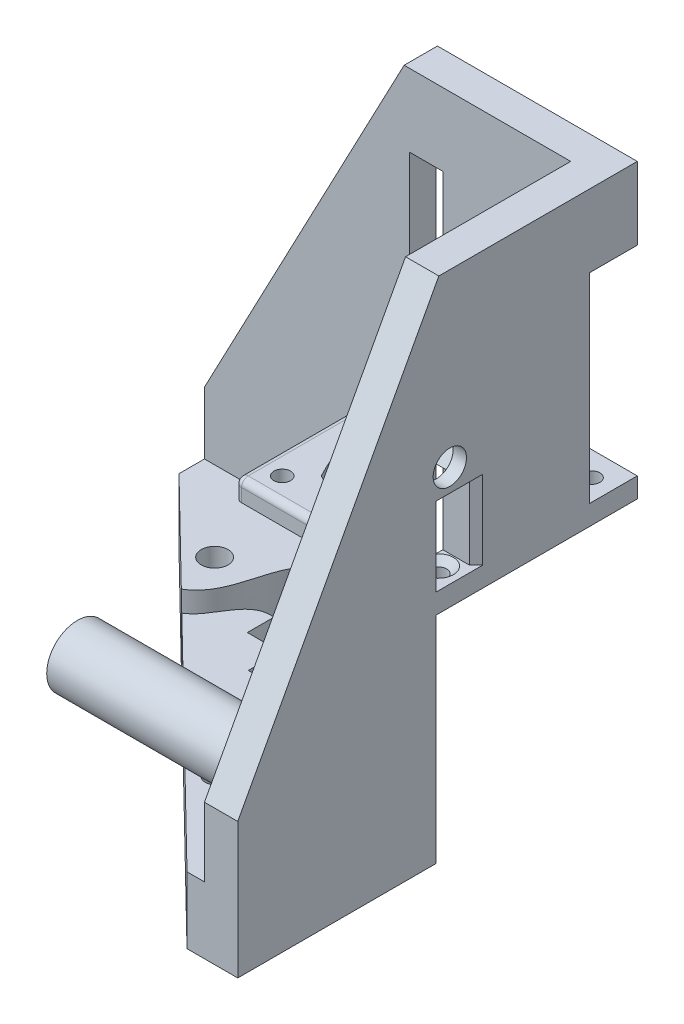
SolidWorks part; units mm, degrees
ref_plane "Front" through (0, 0, 0) normal (0, 0, 1) x (1, 0, 0)
ref_plane "Top" through (0, 0, 0) normal (0, 1, 0) x (1, 0, 0)
ref_plane "Right" through (0, 0, 0) normal (1, 0, 0) x (0, 0, -1)
sketch "Sketch1" plane through (0, 0, 0) normal (0, 1, 0) x (1, 0, 0)
  line L0 (-34.4663, 5.5479) -> (17.9137, -45.6289)
  line L1 (-34.4663, 14.3711) -> (25.5337, 14.3711)
  line L2 (-34.4663, 14.3711) -> (-34.4663, -45.6289)
  line L3 (-34.4663, -45.6289) -> (25.5337, -45.6289)
  line L4 (25.5337, 14.3711) -> (25.5337, -45.6289)
  circle A0 centre (7.6521, -31.0695) radius 1.5601
  circle A1 centre (-20.9229, -2.6469) radius 2.0092
  dimension "D3" = 17.8816
  dimension "D4" = 45.4406
  dimension "D5" = 17.018
  dimension "D6" = 46.4566
  dimension "D1" = 60
  dimension "D2" = 60
extrude "Boss-Extrude1" add sketch "Sketch1" along normal blind 10 contours L4 L1 L2 L0 L3
sketch "Sketch3" plane through (0, 10, 0) normal (0, 1, 0) x (1, 0, 0)
  line L0 (-34.4663, 9.3711) -> (20.5337, 9.3711)
  line L1 (20.5337, 9.3711) -> (20.5337, -45.6289)
  line L5 (25.5337, -45.6289) -> (25.5337, 14.3711)
  line L6 (25.5337, 14.3711) -> (-34.4663, 14.3711)
  line L7 (-34.4663, 14.3711) -> (-34.4663, 5.5479)
  line L8 (-34.4663, 5.5479) -> (17.9137, -45.6289)
  line L9 (17.9137, -45.6289) -> (25.5337, -45.6289)
  line L10 (25.5337, -45.6289) -> (25.5337, 14.3711)
  line L11 (25.5337, 14.3711) -> (-34.4663, 14.3711)
  line L12 (-34.4663, 14.3711) -> (-34.4663, 5.5479)
  line L13 (-34.4663, 5.5479) -> (17.9137, -45.6289)
  line L14 (17.9137, -45.6289) -> (25.5337, -45.6289)
  line M8 (25.5337, -45.6289) -> (25.5337, 14.3711)
  line M9 (25.5337, 14.3711) -> (-34.4663, 14.3711)
  line M10 (-34.4663, 14.3711) -> (-34.4663, 5.5479)
  line M12 (17.9137, -45.6289) -> (25.5337, -45.6289)
  dimension "D2" = 5
  dimension "D3" = 5
  dimension "D1" = 0
extrude "Boss-Extrude3" add sketch "Sketch3" along normal blind 76.2 from surface at -10 contours L0 L1 M12 M8 M9 M10 | L11 L12 L13 L14 L10
sketch "Sketch4" plane through (0, 10, 0) normal (0, 1, 0) x (1, 0, 0)
  line L1 (25.5337, 14.3711) -> (-3.6763, 14.3711)
  line L2 (25.5337, 14.3711) -> (25.5337, -14.8389)
  line L3 (25.5337, -14.8389) -> (-3.6763, -14.8389)
  line L4 (-3.6763, 14.3711) -> (-3.6763, -14.8389)
  line L5 (20.5337, -45.6289) -> (20.5337, 9.3711)
  line L6 (-34.4663, 9.3711) -> (20.5337, 9.3711)
  line L7 (20.5337, 9.3711) -> (20.5337, -45.6289)
  line L8 (20.5337, -45.6289) -> (25.5337, -45.6289)
  line L9 (25.5337, -45.6289) -> (25.5337, 14.3711)
  line L10 (25.5337, 14.3711) -> (-34.4663, 14.3711)
  line L11 (-34.4663, 14.3711) -> (-34.4663, 9.3711)
  line L12 (-34.4663, 9.3711) -> (20.5337, 9.3711)
  line L13 (20.5337, 9.3711) -> (20.5337, -45.6289)
  line L14 (20.5337, -45.6289) -> (25.5337, -45.6289)
  line L15 (25.5337, -45.6289) -> (25.5337, 14.3711)
  line L16 (25.5337, 14.3711) -> (-34.4663, 14.3711)
  line L17 (-34.4663, 14.3711) -> (-34.4663, 9.3711)
  line L18 (20.5337, 9.3711) -> (-34.4663, 9.3711)
  line L19 (-34.4663, 9.3711) -> (-34.4663, 5.5479)
  line L20 (-34.4663, 5.5479) -> (17.9137, -45.6289)
  line L21 (17.9137, -45.6289) -> (20.5337, -45.6289)
  line L22 (20.5337, -45.6289) -> (20.5337, 9.3711)
  line L23 (20.5337, 9.3711) -> (-34.4663, 9.3711)
  line L24 (-34.4663, 9.3711) -> (-34.4663, 5.5479)
  line L25 (-34.4663, 5.5479) -> (17.9137, -45.6289)
  line L26 (17.9137, -45.6289) -> (20.5337, -45.6289)
  dimension "D3" = 29.21
  dimension "D4" = 29.21
  dimension "D1" = 0
  dimension "D2" = 0
extrude "Cut-Extrude1" cut sketch "Sketch4" against normal up to next and the other way blind 22.3 contours L1 L4 L3 L2
sketch "Sketch5" plane through (0, 32.3, 0) normal (0, -1, 0) x (1, 0, 0)
  line L0 (-3.6763, 14.8389) -> (25.5337, 14.8389) construction
  line L1 (-3.6763, 14.8389) -> (-3.6763, -14.3711) construction
  line L2 (25.5337, -14.3711) -> (-3.6763, -14.3711) construction
  line L3 (25.5337, -14.3711) -> (25.5337, 14.8389) construction
  line L4 (-3.6763, 14.8389) -> (25.5337, 14.8389)
  line L5 (-3.6763, 14.8389) -> (-3.6763, -14.3711)
  line L6 (25.5337, -14.3711) -> (-3.6763, -14.3711)
  line L7 (25.5337, -14.3711) -> (25.5337, 14.8389)
  line L9 (21.8237, 12.3389) -> (-1.1763, 12.3389)
  line L10 (21.8237, 12.3389) -> (21.8237, -10.6611)
  line L11 (21.8237, -10.6611) -> (-1.1763, -10.6611)
  line L12 (-1.1763, 12.3389) -> (-1.1763, -10.6611)
  line L13 (25.5337, -14.3711) -> (19.3237, -14.3711)
  line L14 (25.5337, -14.3711) -> (25.5337, -8.1611)
  line L15 (25.5337, -8.1611) -> (19.3237, -8.1611)
  line L16 (19.3237, -14.3711) -> (19.3237, -8.1611)
  line L17 (-3.6763, -14.3711) -> (1.3237, -14.3711)
  line L18 (-3.6763, -14.3711) -> (-3.6763, -8.1611)
  line L19 (-3.6763, -8.1611) -> (1.3237, -8.1611)
  line L20 (1.3237, -14.3711) -> (1.3237, -8.1611)
  line L21 (25.5337, 14.8389) -> (19.3237, 14.8389)
  line L22 (25.5337, 14.8389) -> (25.5337, 9.8389)
  line L23 (25.5337, 9.8389) -> (19.3237, 9.8389)
  line L24 (19.3237, 14.8389) -> (19.3237, 9.8389)
  line M10 (20.5337, -9.3711) -> (-3.6763, -9.3711)
  line M11 (-3.6763, -9.3711) -> (-3.6763, -14.3711)
  line M12 (-3.6763, -14.3711) -> (25.5337, -14.3711)
  line M13 (25.5337, -14.3711) -> (25.5337, 14.8389)
  line M15 (20.5337, 14.8389) -> (20.5337, -9.3711)
  dimension "D1" = 23
  dimension "D2" = 23
  dimension "D3" = 2.5
  dimension "D4" = 2.5
  dimension "D5" = 2.5
  dimension "D6" = 2.5
  dimension "D7" = 2.5
  dimension "D8" = 2.5
  dimension "D9" = 2.5
extrude "Cut-Extrude2" cut sketch "Sketch5" against normal blind 30 from offset 3 contours L20 L11 L12 M12 M10 M11 | L11 L20 L12 M10 | L20 L19 L12 M10 | L16 L6 L15 L10 L11 M13 | L16 L11 L10 L15 M15 M10 | L16 L15 M10 M15 offset against normal yes
sketch "Sketch6" plane through (0, 32.3, 0) normal (0, -1, 0) x (1, 0, 0)
  line L1 (-3.6763, 14.8389) -> (25.5337, 14.8389) construction
  line L2 (-3.6763, 14.8389) -> (-3.6763, -14.3711) construction
  circle A0 centre (22.3237, 12.2889) radius 1.25
  circle A2 centre (22.3237, -10.7111) radius 1.25
  circle A3 centre (-0.6763, -10.7111) radius 1.25
  dimension "D1" = 2.55
  dimension "D2" = 26
  dimension "D3" = 2.5
  dimension "D4" = 23
  dimension "D5" = 23
extrude "Cut-Extrude3" cut sketch "Sketch6" against normal up to next
chamfer "Chamfer1" distance 1 angle 45 8 edges at (-3.6763, 16.15, -14.3711) (1.3237, 50.3, -14.3711) (19.3237, 50.3, -14.3711) (25.5337, 50.3, -8.1611) (25.5337, 50.3, 9.8389) (25.5337, 16.15, 14.8389) (-3.6763, 50.3, -14.3711) (25.5337, 50.3, 14.8389)
sketch "Sketch7" plane through (0, 0, -9.3711) normal (0, 0, 1) x (1, 0, 0)
  line L0 (-4.4781, 76.2) -> (-34.4663, 19.3455)
  line L1 (-34.4663, 76.2) -> (20.5337, 76.2) construction
  line L2 (-34.4663, 76.2) -> (-34.4663, 10) construction
  line L3 (-34.4663, 19.3455) -> (-34.4663, 76.2)
  line L4 (-34.4663, 76.2) -> (-4.4781, 76.2)
extrude "Cut-Extrude4" cut sketch "Sketch7" against normal up to next
sketch "Sketch8" plane through (20.5337, 0, 0) normal (-1, 0, 0) x (0, 0, 1)
  line L0 (15.4321, 76.2) -> (45.6289, 20.3609)
  line L1 (-9.3711, 76.2) -> (45.6289, 76.2) construction
  line L2 (45.6289, 76.2) -> (45.6289, 10) construction
  line L3 (45.6289, 20.3609) -> (45.6289, 76.2)
  line L4 (45.6289, 76.2) -> (15.4321, 76.2)
  line L5 (-5.5479, 10) -> (45.6289, 10) construction
  circle A0 centre (34.7196, 18.9535) radius 2.6
  line M15 (45.6289, 10) -> (45.6289, 76.2)
  line M16 (45.6289, 76.2) -> (-9.3711, 76.2)
  dimension "D1" = 10.9093
  dimension "D3" = 5.2
  dimension "D2" = 8.9535
extrude "Cut-Extrude5" cut sketch "Sketch8" against normal up to next contours L0 M16 M15
sketch "Sketch9" plane through (0, 32.3, 0) normal (0, -1, 0) x (1, 0, 0)
  line L0 (-4.6763, -14.3711) -> (-4.6763, 15.8389)
  line L1 (-4.6763, 15.8389) -> (25.5337, 15.8389)
  line L2 (25.5337, -14.3711) -> (-13.9259, 25.0885) construction
  line L3 (25.5337, -14.3711) -> (-4.6763, -14.3711) construction
  line L4 (-4.6763, -14.3711) -> (0.9008, -14.3711)
  line L5 (25.5337, 10.2619) -> (25.5337, 15.8389)
  line L6 (25.5337, -14.3711) -> (25.5337, 15.8389) construction
  arc A0 (0.9008, -14.3711) -> (1.8042, 9.3584) centre (25.0313, -3.4078) cw
  arc A1 (25.5337, 10.2619) -> (1.8042, 9.3584) centre (14.5705, -13.8686) ccw
  circle A2 centre (-0.6763, -10.7111) radius 1.25 construction
  circle A3 centre (22.3237, 12.2889) radius 1.25 construction
  circle A4 centre (-0.6763, -10.7111) radius 1.25
  circle A5 centre (22.3237, 12.2889) radius 1.25
  circle A6 centre (-1.1263, 12.2889) radius 1.25
  circle M8 centre (22.3237, 12.2889) radius 1.25
  circle M9 centre (-0.6763, -10.7111) radius 1.25
  line M11 (20.5337, -9.3711) -> (-3.6763, -9.3711)
  line M12 (-3.6763, -9.3711) -> (-3.6763, -13.3711)
  line M13 (-3.6763, -13.3711) -> (-4.6763, -14.3711)
  line M14 (-4.6763, -14.3711) -> (25.5337, -14.3711)
  line M15 (25.5337, -14.3711) -> (25.5337, 15.8389)
  line M16 (25.5337, 15.8389) -> (24.5337, 14.8389)
  line M17 (24.5337, 14.8389) -> (20.5337, 14.8389)
  line M18 (20.5337, 14.8389) -> (20.5337, -9.3711)
  dimension "D1" = 5.5771
extrude "Boss-Extrude4" add sketch "Sketch9" against normal blind 3 contours A0 M14 M9 M11 M12 M13 | A1 M15 M16 M17 M18 M8 | L2 A1 L1 M18 M17 M16 | A0 L2 L0 M13 M12 M11
fillet "Fillet2" radius 1 4 edges at (7.9287, 35.3, 15.8389) (-4.6763, 35.3, 3.2339) (-4.6763, 33.8, 15.8389) (-0.7934, 33.8, -9.3711)
sketch "Sketch10" plane through (0, 32.3, 0) normal (0, -1, 0) x (1, 0, 0)
  line L0 (22.3237, 12.2889) -> (-0.6763, -10.7111) construction
  circle A0 centre (10.8237, 0.7889) radius 11.5
extrude "Cut-Extrude6" cut sketch "Sketch10" against normal blind 3
sketch "Sketch12" plane through (20.5337, 0, 0) normal (-1, 0, 0) x (0, 0, 1)
  line L0 (45.6289, 20.3609) -> (45.6289, 10) construction
  line L1 (-5.5479, 10) -> (45.6289, 10) construction
  circle A0 centre (34.7189, 18.95) radius 2.6
  circle A1 centre (34.7189, 18.95) radius 4.6
  dimension "D1" = 10.91
  dimension "D2" = 8.95
  dimension "D3" = 5.2
  dimension "D4" = 2
extrude "Boss-Extrude5" add sketch "Sketch12" along normal blind 30
fillet "Fillet3" radius 1 1 edges at (-9.4663, 18.95, 37.3189)
chamfer "Chamfer2" distance 1 angle 45 2 edges at (22.3237, 35.3, 13.5389) (-0.6763, 35.3, -11.9611)
sketch "Sketch14" plane through (25.5337, 0, 0) normal (1, 0, 0) x (0, 0, -1)
  line L1 (-19.4539, 65.849) -> (-7.0581, 65.849)
  line L2 (-19.4539, 65.849) -> (-19.4539, 47.1223)
  line L3 (-19.4539, 47.1223) -> (-7.0581, 47.1223)
  line L4 (-7.0581, 65.849) -> (-7.0581, 47.1223)
extrude "Boss-Extrude6" add sketch "Sketch14" against normal up to surface (5 mm away) up to face at (20.5337, 18.95, 30.1189)
sketch "Sketch13" plane through (25.5337, 0, 0) normal (1, 0, 0) x (0, 0, -1)
  line L0 (33, 0) -> (-33, 0) construction
  line L2 (14.3711, 76.2) -> (14.3711, 65.3) construction
  circle A0 centre (-13.7829, 50.506) radius 2.5
  dimension "D1" = 50.506
  dimension "D2" = 5
  dimension "D3" = 28.154
extrude "Cut-Extrude7" cut sketch "Sketch13" against normal blind 20
sketch "Sketch15" plane through (20.5337, 0, 0) normal (-1, 0, 0) x (0, 0, 1)
  line L1 (16.1501, 46.406) -> (18.5172, 50.506)
  line L2 (18.5172, 50.506) -> (16.1501, 54.606)
  line L3 (16.1501, 54.606) -> (11.4158, 54.606)
  line L4 (11.4158, 54.606) -> (9.0487, 50.506)
  line L5 (9.0487, 50.506) -> (11.4158, 46.406)
  line L6 (11.4158, 46.406) -> (16.1501, 46.406)
  circle A0 centre (13.7829, 50.506) radius 4.1 construction
  dimension "D1" = 8.2
extrude "Cut-Extrude8" cut sketch "Sketch15" against normal blind 3
sketch "Sketch19" plane through (0, 10, 0) normal (0, 1, 0) x (1, 0, 0)
  line L0 (-3.6763, -14.8389) -> (-3.6763, 9.3711) construction
  line L3 (-3.6763, 2.8577) -> (-3.5286, -1.6399)
  line L4 (-34.4663, 5.5479) -> (17.9137, -45.6289) construction
  line L5 (-3.6763, 7.518) -> (-8.6763, 7.518)
  line L6 (-3.6763, 7.518) -> (-3.6763, -9.982)
  line L7 (-3.6763, -9.982) -> (-8.6763, -9.982)
  line L8 (-8.6763, 7.518) -> (-8.6763, -9.982)
  line L9 (-19.2829, -9.2868) -> (-16.1211, -12.3759)
  spline S0 degree 3 poles (-8.6763, 5.1248) (-16.8086, 3.7254) (-13.4697, -5.7367) (-19.2829, -9.2868) knots 0 0 0 0 1 1 1 1
  spline S1 degree 3 poles (-8.6763, -5.9903) (-12.9064, -5.582) (-13.1575, -10.6096) (-16.1211, -12.3759) knots 0 0 0 0 1 1 1 1
  line M8 (-3.6763, -14.8389) -> (-3.6763, 9.3711)
  line M11 (-34.4663, 5.5479) -> (17.9137, -45.6289)
  dimension "D2" = 17.5
  dimension "D3" = 5
extrude "Cut-Extrude11" cut sketch "Sketch19" against normal up to surface (10 mm away) contours L5 L8 L7 M8 | S1 L8 S0 M11 up to face at (-20.9229, 0, 4.6562)
sketch "Sketch20" plane through (0, 0, 0) normal (0, -1, 0) x (1, 0, 0)
  line L0 (-16.1211, 12.3759) -> (-19.2829, 9.2868)
  line L1 (-11.6454, 6.9036) -> (-13.3713, -2.1969)
  line L7 (-3.6763, -13.3711) -> (-3.6763, -7.518)
  line L8 (-3.6763, -7.518) -> (-8.6763, -7.518)
  line L9 (-8.6763, -7.518) -> (-8.6763, -5.1248)
  line L10 (-19.2829, 9.2868) -> (-34.4663, -5.5479)
  line L11 (-34.4663, -5.5479) -> (-34.4663, -14.3711)
  line L12 (-34.4663, -14.3711) -> (-4.6763, -14.3711)
  line L13 (-4.6763, -14.3711) -> (-3.6763, -13.3711)
  line L14 (-3.6763, -13.3711) -> (-3.6763, -7.518)
  line L15 (-3.6763, -7.518) -> (-8.6763, -7.518)
  line L16 (-8.6763, -7.518) -> (-8.6763, -5.1248)
  line L18 (-34.4663, -5.5479) -> (-34.4663, -14.3711)
  line L19 (-34.4663, -14.3711) -> (-4.6763, -14.3711)
  line L20 (-4.6763, -14.3711) -> (-3.6763, -13.3711)
  line L24 (-8.6763, 9.982) -> (-3.6763, 9.982)
  line L25 (-3.6763, 9.982) -> (-3.6763, 14.8389)
  line L26 (-3.6763, 14.8389) -> (24.5337, 14.8389)
  line L27 (24.5337, 14.8389) -> (25.5337, 15.8389)
  line L28 (25.5337, 15.8389) -> (25.5337, 45.6289)
  line L29 (25.5337, 45.6289) -> (17.9137, 45.6289)
  line L30 (25.5337, 45.6289) -> (17.9137, 45.6289)
  line L32 (17.9137, 45.6289) -> (-16.1211, 12.3759)
  line L33 (-8.6763, 5.9903) -> (-8.6763, 9.982)
  line L34 (-8.6763, 9.982) -> (-3.6763, 9.982)
  line L35 (-3.6763, 9.982) -> (-3.6763, 14.8389)
  line L36 (-3.6763, 14.8389) -> (24.5337, 14.8389)
  line L37 (24.5337, 14.8389) -> (25.5337, 15.8389)
  line L38 (25.5337, 15.8389) -> (25.5337, 45.6289)
  line L43 (-8.6763, 5.9903) -> (-8.6763, 9.982)
  spline S1 degree 3 poles (2508.471, 1626.2699) (-2509.8728, -1731.0075) (2485.2815, 1725.4852) (-2556.1237, -1590.5651) knots -4.391317 -4.391317 -4.391317 -4.391317 5.515159 5.515159 5.515159 5.515159 only from (-8.6763, -5.1248) to (-19.2829, 9.2868)
  spline S2 degree 3 poles (-13.3713, -2.1969) (-15.6401, 1.2833) (-15.1622, 6.7703) (-19.2829, 9.2868) knots 0.291157 0.291157 0.291157 0.291157 1 1 1 1
  spline S3 degree 3 poles (-1908.7552, -2314.5903) (1822.787, 2419.9812) (-1839.4344, -2410.1542) (1850.61, 2360.0163) knots -6.119432 -6.119432 -6.119432 -6.119432 6.893559 6.893559 6.893559 6.893559 only from (-16.1211, 12.3759) to (-8.6763, 5.9903)
  spline S4 degree 3 poles (-16.1211, 12.3759) (-14.0692, 11.1529) (-13.3176, 8.3667) (-11.6454, 6.9036) knots 0 0 0 0 0.692365 0.692365 0.692365 0.692365
  spline M25 degree 3 poles (-19.2829, 9.2868) (-13.4697, 5.7367) (-16.8086, -3.7254) (-8.6763, -5.1248) knots 0 0 0 0 1 1 1 1
  dimension "D1" = 0
  dimension "D2" = 0
extrude "Boss-Extrude8" add sketch "Sketch20" against normal blind 3 contours S4 L0 L1 M25
